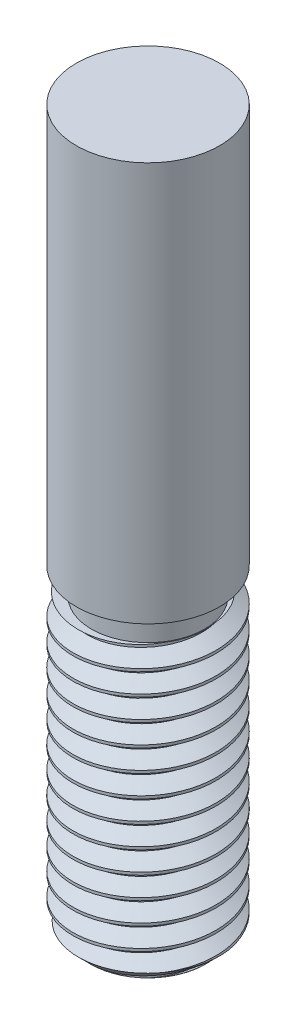
SolidWorks part; units mm, degrees
ref_plane "Front Plane" through (0, 0, 0) normal (0, 0, 1) x (1, 0, 0)
ref_plane "Top Plane" through (0, 0, 0) normal (0, 1, 0) x (1, 0, 0)
ref_plane "Right Plane" through (0, 0, 0) normal (1, 0, 0) x (0, 0, -1)
sketch "Sketch2" plane through (0, 0, 0) normal (0, 0, 1) x (1, 0, 0)
  line L0 (0, -14.2875) -> (0, -77.7875)
  line L1 (6.35, -14.2875) -> (0, -14.2875)
  line L7 (6.35, -14.2875) -> (6.35, -77.7875)
  line L8 (6.35, -77.7875) -> (0, -77.7875)
  dimension "D1" = 6.35
  dimension "D2" = 63.5
revolve "Shaft" add sketch "Sketch2" angle 360 about L0
ref_plane "Plane1" through (0, 12.7, 0) normal (0, 1, 0) x (1, 0, 0)
ref_plane "Plane2" through (0, 0, 12.7) normal (0, 0, 1) x (1, 0, 0)
chamfer "End" distance 1.27 angle 45 1 edges at (-6.35, -77.7875, 0)
sketch "Sketch10" plane through (0, -77.7875, 0) normal (0, -1, 0) x (1, 0, 0)
  circle A0 centre (0, 0) radius 6.35
curve "Helix/Spiral1" pitch 1.9538 height 27.3538 radius 6.35 centre (0, -77.7875, 0) axis (0, 1, 0) start towards (0, 0, 1)
sketch "Sketch11" plane through (0, 0, 0) normal (1, 0, 0) x (0, 0, -1)
  line L0 (-6.35, -77.0543) -> (-6.35, -79.0081) construction
  line L1 (-6.35, -79.0081) -> (-6.35, -78.7644) construction
  line L2 (-6.35, -78.7644) -> (-6.944, -78.7644)
  line L3 (-6.35, -78.7644) -> (-5.08, -78.0312)
  line L4 (-5.08, -78.0312) -> (-5.08, -77.7875)
  line L5 (-5.08, -77.7875) -> (-6.35, -77.0543)
  line L6 (-6.944, -78.7644) -> (-6.944, -77.0543)
  line L7 (-6.944, -77.0543) -> (-6.35, -77.0543)
  line L8 (-5.08, -77.7875) -> (5.08, -77.7875) construction
  line L19 (-6.35, -14.2875) -> (-6.35, -76.5175) construction
  dimension "D1" = 1.9538
  dimension "D2" = 60
  dimension "D3" = 60
  dimension "D4" = 1.27
sweep "Threads" cut profiles "Sketch11" path "Helix/Spiral1"
sketch "Sketch12" plane through (0, 0, 0) normal (-1, 0, 0) x (0, 0, 1)
  line L2 (5.0165, -49.7004) -> (7.6835, -49.7004)
  line L3 (5.0165, -49.7004) -> (5.0165, -52.0817)
  line L4 (5.0165, -52.0817) -> (7.6835, -52.0817)
  line L5 (7.6835, -49.7004) -> (7.6835, -52.0817)
  point P0 (6.35, -49.7004)
  dimension "D1" = 2.667
  dimension "D2" = 2.3813
revolve "Inset" cut sketch "Sketch12" angle 360 about axis through (0, -14.2875, 0) along (0, 1, 0)
